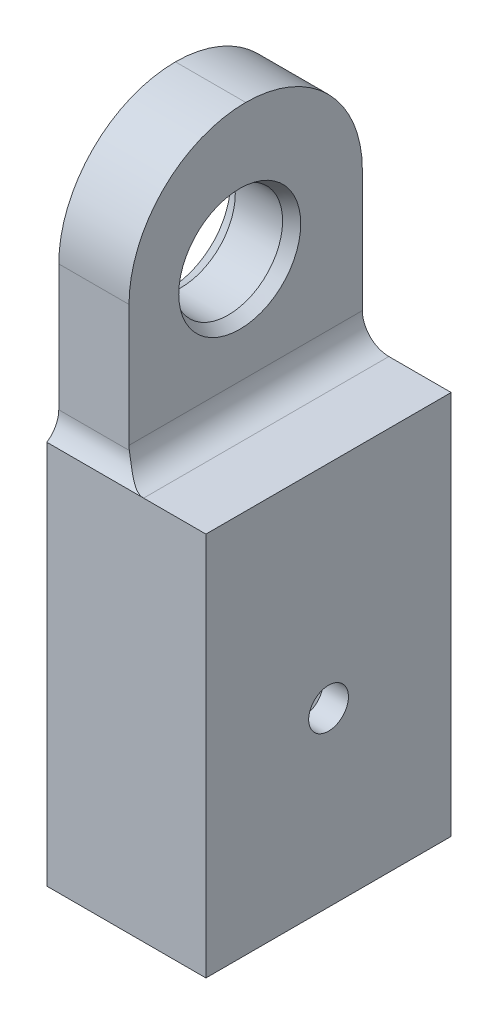
SolidWorks part; units mm, degrees
ref_plane "Front Plane" through (0, 0, 0) normal (0, 0, 1) x (1, 0, 0)
ref_plane "Top Plane" through (0, 0, 0) normal (0, 1, 0) x (1, 0, 0)
ref_plane "Right Plane" through (0, 0, 0) normal (1, 0, 0) x (0, 0, -1)
sketch "Sketch1" plane through (0, 0, 0) normal (0, 1, 0) x (1, 0, 0)
  line L1 (-6, -9.25) -> (6, -9.25)
  line L2 (-6, -9.25) -> (-6, 9.25)
  line L3 (-6, 9.25) -> (6, 9.25)
  line L4 (6, -9.25) -> (6, 9.25)
  line L5 (-6, -9.25) -> (6, 9.25) construction
  line L6 (-6, 9.25) -> (6, -9.25) construction
  point P0 (0, 0)
  dimension "D1" = 12
  dimension "D2" = 18.5
extrude "Boss-Extrude1" add sketch "Sketch1" along normal blind 29
sketch "Sketch2" plane through (0, 0, 0) normal (0, -1, 0) x (1, 0, 0)
  line L1 (-4.1, -7.6) -> (4.1, -7.6)
  line L2 (-4.1, -7.6) -> (-4.1, 7.6)
  line L3 (-4.1, 7.6) -> (4.1, 7.6)
  line L4 (4.1, -7.6) -> (4.1, 7.6)
  line L5 (-4.1, -7.6) -> (4.1, 7.6) construction
  line L6 (-4.1, 7.6) -> (4.1, -7.6) construction
  point P0 (0, 0)
  dimension "D1" = 8.2
  dimension "D2" = 15.2
extrude "Cut-Extrude1" cut sketch "Sketch2" against normal blind 23
sketch "Sketch4" plane through (0, 29, 0) normal (0, 1, 0) x (1, 0, 0)
  line L5 (-6, -8.35) -> (-0.7, -8.35)
  line L6 (-6, -8.35) -> (-6, 9.25)
  line L7 (-6, 9.25) -> (-0.7, 9.25)
  line L8 (-0.7, -8.35) -> (-0.7, 9.25)
  line L9 (-6, -8.35) -> (-0.7, 9.25) construction
  line L10 (-6, 9.25) -> (-0.7, -8.35) construction
  point P0 (-3.35, 0.45)
  point P5 (0, 0)
  dimension "D1" = 5.3
  dimension "D2" = 17.6
extrude "Boss-Extrude2" add sketch "Sketch4" along normal blind 20
sketch "Sketch5" plane through (-0.7, 0, 0) normal (1, 0, 0) x (0, 0, -1)
  line L0 (-8.35, 49) -> (9.25, 49) construction
  circle A0 centre (0, 39) radius 4.1
  dimension "D2" = 8.2
  dimension "D1" = 10
extrude "Cut-Extrude2" cut sketch "Sketch5" against normal up to next
fillet "Fillet1" radius 8.8 2 edges at (-3.35, 49, -9.25) (-3.35, 49, 8.35)
fillet "Fillet2" [suppressed] radius 2
sketch "Sketch6" plane through (6, 0, 0) normal (1, 0, 0) x (0, 0, -1)
  line L0 (-7.6, 23) -> (7.6, 23) construction
  circle A0 centre (0, 13) radius 1.5
  dimension "D2" = 3
  dimension "D1" = 10
extrude "Cut-Extrude3" cut sketch "Sketch6" against normal through all
chamfer "Chamfer1" distance 0.5 angle 60 2 edges at (-0.7, 39, -4.1) (-6, 39, -4.1) first distance on face at (-0.7, 39, -4.1) first distance on face at (-6, 13, -1.5)
fillet "Fillet6" radius 2 2 edges at (-0.7, 29, -0.45) (-3.35, 29, 8.35)
